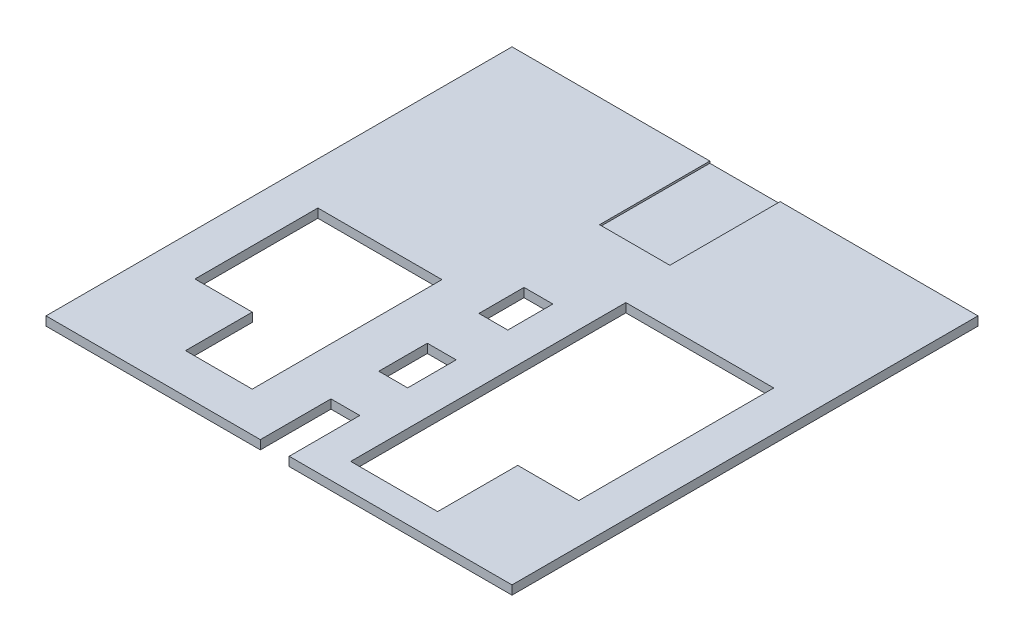
SolidWorks part; units mm, degrees
ref_plane "Front Plane" through (0, 0, 0) normal (0, 0, 1) x (1, 0, 0)
ref_plane "Top Plane" through (0, 0, 0) normal (0, 1, 0) x (1, 0, 0)
ref_plane "Right Plane" through (0, 0, 0) normal (1, 0, 0) x (0, 0, -1)
sketch "Sketch1" plane through (0, 0, 0) normal (0, 1, 0) x (1, 0, 0)
  line L1 (0, 0) -> (120, 0)
  line L2 (0, 0) -> (0, 120)
  line L3 (0, 120) -> (120, 120)
  line L4 (120, 0) -> (120, 120)
  dimension "D1" = 120
  dimension "D2" = 120
extrude "Boss-Extrude1" add sketch "Sketch1" along normal blind 2.3
sketch "Sketch2" plane through (0, 2.3, 0) normal (0, 1, 0) x (1, 0, 0)
  line L0 (0, 0) -> (120, 0) construction
  line L1 (0, 68.6) -> (53.3, 68.6) construction
  line L2 (0, 68.6) -> (0, 0) construction
  line L3 (0, 0) -> (53.3, 0) construction
  line L4 (53.3, 68.6) -> (53.3, 0) construction
  line L5 (64, 85) -> (120, 85) construction
  line L6 (64, 85) -> (64, 0) construction
  line L7 (64, 0) -> (120, 0) construction
  line L8 (120, 85) -> (120, 0) construction
  line L9 (0, 120) -> (0, 0) construction
  line L10 (51.65, 120) -> (68.35, 120) construction
  line L11 (51.65, 120) -> (51.65, 92.3) construction
  line L12 (51.65, 92.3) -> (68.35, 92.3) construction
  line L13 (68.35, 120) -> (68.35, 92.3) construction
  line L14 (120, 0) -> (120, 120) construction
  line L15 (120, 120) -> (0, 120) construction
  line L16 (50.95, 120) -> (50.95, 91.6)
  line L17 (50.95, 91.6) -> (69.05, 91.6)
  line L18 (69.05, 120) -> (69.05, 91.6)
  line L19 (50.95, 120) -> (69.05, 120)
  line L21 (10.9506, 59.0584) -> (42.8973, 59.0584)
  line L22 (10.9506, 59.0584) -> (10.9506, 10.2106)
  line L23 (10.9506, 10.2106) -> (42.8973, 10.2106)
  line L24 (42.8973, 59.0584) -> (42.8973, 10.2106)
  line L25 (71.6957, 77.6209) -> (109.7905, 77.6209)
  line L26 (71.6957, 77.6209) -> (71.6957, 6.7704)
  line L27 (71.6957, 6.7704) -> (109.7905, 6.7704)
  line L28 (109.7905, 77.6209) -> (109.7905, 6.7704)
  line L29 (55.2019, 0) -> (62.6241, 0)
  line L30 (55.2019, 0) -> (55.2019, 18.178)
  line L31 (55.2019, 18.178) -> (62.6241, 18.178)
  line L32 (62.6241, 0) -> (62.6241, 18.178)
  line L33 (55.2019, 30.4982) -> (62.6241, 30.4982)
  line L34 (55.2019, 30.4982) -> (55.2019, 42.9966)
  line L35 (55.2019, 42.9966) -> (62.6241, 42.9966)
  line L36 (62.6241, 30.4982) -> (62.6241, 42.9966)
  line L37 (55.2019, 56.2836) -> (62.6241, 56.2836)
  line L38 (55.2019, 56.2836) -> (55.2019, 67.8974)
  line L39 (55.2019, 67.8974) -> (62.6241, 67.8974)
  line L40 (62.6241, 56.2836) -> (62.6241, 67.8974)
  line L41 (109.7905, 6.7704) -> (94.0804, 6.7704)
  line L42 (109.7905, 6.7704) -> (109.7905, 27.3968)
  line L43 (109.7905, 27.3968) -> (94.0804, 27.3968)
  line L44 (94.0804, 6.7704) -> (94.0804, 27.3968)
  line L45 (10.9506, 10.2106) -> (25.7199, 10.2106)
  line L46 (10.9506, 10.2106) -> (10.9506, 27.3968)
  line L47 (10.9506, 27.3968) -> (25.7199, 27.3968)
  line L48 (25.7199, 10.2106) -> (25.7199, 27.3968)
  line M146 (0, 0) -> (120, 0)
  line M148 (120, 120) -> (0, 120)
  dimension "D1" = 68.6
  dimension "D2" = 53.3
  dimension "D3" = 56
  dimension "D4" = 85
  dimension "D5" = 27.7
  dimension "D6" = 16.7
  dimension "D7" = 51.65
  dimension "D8" = 0.7
extrude "Cut-Extrude1" cut sketch "Sketch2" against normal up to next contours L24 L21 L22 L23 | L32 L31 L30 M146 | L33 L36 L35 L34 | L37 L40 L39 L38 | L28 L25 L26 L27 region at (28.5923, 2.3, -37.7096) region at (89.216, 2.3, -45.6219) region at (58.913, 2.3, -9.089) region at (58.913, 2.3, -36.7474) region at (58.913, 2.3, -62.0905)
extrude "Cut-Extrude2" cut sketch "Sketch2<3>" against normal blind 0.5 contours L18 L16 L17 M148 region at (60, 2.3, -105.8)
sketch "Sketch2<3>" plane through (0, 2.3, 0) normal (0, 1, 0) x (1, 0, 0) same geometry as "Sketch2"
equation "\"D7@Sketch2\"=(\"D2@sketch1\"-\"D6@Sketch2\")/2"
